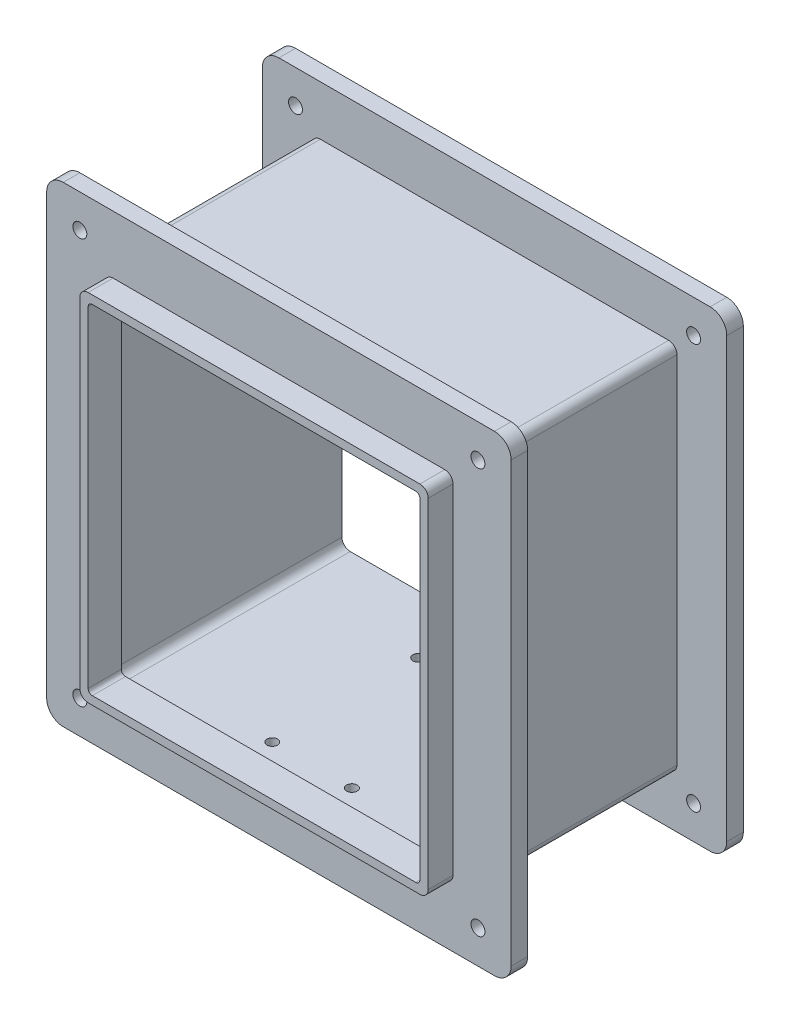
SolidWorks part; units mm, degrees
ref_plane "前视基准面" through (0, 0, 0) normal (0, 0, 1) x (1, 0, 0)
ref_plane "上视基准面" through (0, 0, 0) normal (0, 1, 0) x (1, 0, 0)
ref_plane "右视基准面" through (0, 0, 0) normal (1, 0, 0) x (0, 0, -1)
sketch "草图4" plane through (0, 0, 0) normal (0, 0, 1) x (1, 0, 0)
  line L1 (-105, -107.125) -> (105, -107.125)
  line L2 (-105, -107.125) -> (-105, 107.125)
  line L3 (-105, 107.125) -> (105, 107.125)
  line L4 (105, -107.125) -> (105, 107.125)
  line L5 (-105, -107.125) -> (105, 107.125) construction
  line L6 (-105, 107.125) -> (105, -107.125) construction
  line L7 (-110, -112.125) -> (110, -112.125)
  line L8 (-110, -112.125) -> (-110, 112.125)
  line L9 (-110, 112.125) -> (110, 112.125)
  line L10 (110, -112.125) -> (110, 112.125)
  line L11 (-110, -112.125) -> (110, 112.125) construction
  line L12 (-110, 112.125) -> (110, -112.125) construction
  point P0 (0, 0)
  point P6 (0, 0)
  dimension "D1" = 210
  dimension "D2" = 214.25
  dimension "D3" = 5
  dimension "D4" = 5
extrude "凸台-拉伸7" add sketch "草图4" along normal blind 120
sketch "草图7" plane through (0, 0, 0) normal (0, 0, -1) x (-1, 0, 0)
  line L0 (-110, 112.125) -> (110, 112.125) construction
  line L1 (140, 142.125) -> (-140, 142.125)
  line L2 (140, 142.125) -> (140, -142.125)
  line L3 (140, -142.125) -> (-140, -142.125)
  line L4 (-140, 142.125) -> (-140, -142.125)
  line L5 (140, 142.125) -> (-140, -142.125) construction
  line L6 (140, -142.125) -> (-140, 142.125) construction
  line L7 (-110, -112.125) -> (-110, 112.125) construction
  line L8 (105, -107.125) -> (-105, -107.125) construction
  line L9 (105, 107.125) -> (105, -107.125) construction
  line L10 (-105, 107.125) -> (105, 107.125) construction
  line L11 (-105, -107.125) -> (-105, 107.125) construction
  line L12 (105, -107.125) -> (-105, -107.125)
  line L13 (105, 107.125) -> (105, -107.125)
  line L14 (-105, 107.125) -> (105, 107.125)
  line L15 (-105, -107.125) -> (-105, 107.125)
  point P0 (0, 0)
  dimension "D1" = 30
  dimension "D2" = 30
extrude "凸台-拉伸8" add sketch "草图7" along normal blind 10
sketch "草图8" plane through (0, 0, 120) normal (0, 0, 1) x (1, 0, 0)
  line L1 (140, -142.125) -> (-140, -142.125)
  line L2 (140, -142.125) -> (140, 142.125)
  line L3 (140, 142.125) -> (-140, 142.125)
  line L4 (-140, -142.125) -> (-140, 142.125)
  line L5 (140, -142.125) -> (-140, 142.125) construction
  line L6 (140, 142.125) -> (-140, -142.125) construction
  line L7 (105, -107.125) -> (105, 107.125) construction
  line L8 (-105, -107.125) -> (105, -107.125) construction
  line L9 (-105, 107.125) -> (-105, -107.125) construction
  line L10 (105, 107.125) -> (-105, 107.125) construction
  line L11 (105, -107.125) -> (105, 107.125)
  line L12 (-105, -107.125) -> (105, -107.125)
  line L13 (-105, 107.125) -> (-105, -107.125)
  line L14 (105, 107.125) -> (-105, 107.125)
  point P0 (0, 0)
  point P11 (-117.2762, 126.0676)
extrude "凸台-拉伸9" add sketch "草图8" along normal blind 10
fillet "圆角5" radius 5 8 edges at (-105, 107.125, 60) (-110, 112.125, 60) (105, -107.125, 60) (110, -112.125, 60) (-105, -107.125, 60) (-110, -112.125, 60) (110, 112.125, 60) (105, 107.125, 60)
fillet "圆角6" radius 10 8 edges at (140, 142.125, 125) (140, -142.125, 125) (-140, -142.125, 125) (-140, 142.125, 125) (-140, 142.125, -5) (-140, -142.125, -5) (140, -142.125, -5) (140, 142.125, -5)
hole_wizard "Ø8.4 (8.4) 直径孔1" positions "草图16" profile "草图17" hole size "Ø8.4" standard "GB" end condition through all
sketch "草图16" plane through (0, 0, -10) normal (0, 0, -1) x (-1, 0, 0)
  line L0 (130, 142.125) -> (-130, 142.125) construction
  line L1 (-140, 132.125) -> (-140, -132.125) construction
  line L2 (140, -132.125) -> (140, 132.125) construction
  line L3 (-130, -142.125) -> (130, -142.125) construction
  point P0 (120, -122.125)
  point P3 (120, 122.125)
  point P6 (-120, 122.125)
  point P9 (-120, -122.125)
  dimension "D1" = 20
  dimension "D2" = 20
  dimension "D3" = 20
  dimension "D4" = 20
  dimension "D5" = 20
  dimension "D6" = 20
  dimension "D7" = 20
  dimension "D8" = 20
sketch "草图17" plane through (-120, -122.125, -10) normal (1, 0, 0) x (0, 1, 0)
  line L0 (0, 0) -> (0, 140)
  line L1 (0, 140) -> (4.2, 140)
  line L2 (4.2, 140) -> (4.2, 0)
  line L5 (4.2, 0) -> (0, 0)
  line L11 (0, -6.35) -> (0, 107.95) construction
  dimension "通孔孔直径" = 8.4
  dimension "通孔孔深度" = 140
sketch "草图18" plane through (0, -112.125, 0) normal (0, -1, 0) x (1, 0, 0)
  line L0 (-130, 130) -> (130, 130) construction
  line L5 (105, 0) -> (105, 120) construction
  point P0 (-24, 110)
  point P1 (-24, 22)
  point P2 (24, 22)
  point P3 (24, 110)
  dimension "D1" = 48
  dimension "D2" = 48
  dimension "D3" = 88
  dimension "D4" = 88
  dimension "D5" = 100.2397
  dimension "D6" = 20
  dimension "D7" = 20
  dimension "D8" = 81
hole_wizard "Ø6.4 (6.4) 直径孔1" positions "草图21" profile "草图22" hole size "Ø6.4" standard "GB" end condition up to next
sketch "草图21" plane through (0, -112.125, 0) normal (0, -1, 0) x (-1, 0, 0)
  point P0 (24, -110)
  point P3 (-24, -110)
  point P6 (-24, -22)
  point P9 (24, -22)
sketch "草图22" plane through (-24, -112.125, 110) normal (1, 0, 0) x (0, 0, -1)
  line L0 (0, 0) -> (0, 5)
  line L1 (0, 5) -> (3.2, 5)
  line L2 (3.2, 5) -> (3.2, 0)
  line L5 (3.2, 0) -> (0, 0)
  line L11 (0, -6.35) -> (0, 107.95) construction
  dimension "通孔孔直径" = 6.4
  dimension "通孔孔深度" = 5
sketch "草图24" plane through (0, 0, 130) normal (0, 0, 1) x (1, 0, 0)
  line L0 (105, -102.125) -> (105, 102.125) construction
  line L1 (-100, -107.125) -> (100, -107.125) construction
  line L2 (-105, 102.125) -> (-105, -102.125) construction
  line L3 (100, 107.125) -> (-100, 107.125) construction
  line L4 (105, -102.125) -> (105, 102.125)
  line L5 (-100, -107.125) -> (100, -107.125)
  line L6 (-105, 102.125) -> (-105, -102.125)
  line L7 (100, 107.125) -> (-100, 107.125)
  line L9 (100, -102.125) -> (-100, -102.125)
  line L10 (100, -102.125) -> (100, 102.125)
  line L11 (100, 102.125) -> (-100, 102.125)
  line L12 (-100, -102.125) -> (-100, 102.125)
  line L13 (100, -102.125) -> (-100, 102.125) construction
  line L14 (100, 102.125) -> (-100, -102.125) construction
  arc A0 (105, 102.125) -> (100, 107.125) centre (100, 102.125) ccw construction
  arc A1 (100, -107.125) -> (105, -102.125) centre (100, -102.125) ccw construction
  arc A2 (-105, -102.125) -> (-100, -107.125) centre (-100, -102.125) ccw construction
  arc A3 (-100, 107.125) -> (-105, 102.125) centre (-100, 102.125) ccw construction
  arc A4 (105, 102.125) -> (100, 107.125) centre (100, 102.125) ccw
  arc A5 (100, -107.125) -> (105, -102.125) centre (100, -102.125) ccw
  arc A6 (-105, -102.125) -> (-100, -107.125) centre (-100, -102.125) ccw
  arc A7 (-100, 107.125) -> (-105, 102.125) centre (-100, 102.125) ccw
  point P12 (0, 0)
  dimension "D1" = 5
  dimension "D2" = 5
extrude "凸台-拉伸10" add sketch "草图24" along normal blind 15 separate body
sketch "草图25" plane through (0, 0, 130) normal (0, 0, -1) x (-1, 0, 0)
  line L0 (100, -102.125) -> (-100, -102.125) construction
  line L1 (-100, -102.125) -> (-100, 102.125) construction
  line L2 (100, 102.125) -> (100, -102.125) construction
  line L3 (-100, 102.125) -> (100, 102.125) construction
  line L4 (105, -102.125) -> (105, 102.125) construction
  line L5 (-100, -107.125) -> (100, -107.125) construction
  line L6 (-105, 102.125) -> (-105, -102.125) construction
  line L7 (100, 107.125) -> (-100, 107.125) construction
  line L8 (100, -102.125) -> (-100, -102.125)
  line L9 (-100, -102.125) -> (-100, 102.125)
  line L10 (100, 102.125) -> (100, -102.125)
  line L11 (-100, 102.125) -> (100, 102.125)
  line L12 (105, -102.125) -> (105, 102.125)
  line L13 (-100, -107.125) -> (100, -107.125)
  line L14 (-105, 102.125) -> (-105, -102.125)
  line L15 (100, 107.125) -> (-100, 107.125)
  arc A0 (105, 102.125) -> (100, 107.125) centre (100, 102.125) ccw construction
  arc A1 (100, -107.125) -> (105, -102.125) centre (100, -102.125) ccw construction
  arc A2 (-105, -102.125) -> (-100, -107.125) centre (-100, -102.125) ccw construction
  arc A3 (-100, 107.125) -> (-105, 102.125) centre (-100, 102.125) ccw construction
  arc A4 (105, 102.125) -> (100, 107.125) centre (100, 102.125) ccw
  arc A5 (100, -107.125) -> (105, -102.125) centre (100, -102.125) ccw
  arc A6 (-105, -102.125) -> (-100, -107.125) centre (-100, -102.125) ccw
  arc A7 (-100, 107.125) -> (-105, 102.125) centre (-100, 102.125) ccw
extrude "凸台-拉伸11" add sketch "草图25" along normal blind 5
fillet "圆角7" radius 2.5 12 edges at (103.5355, -105.6605, 125) (105, 0, 125) (103.5355, 105.6605, 125) (0, 107.125, 125) (-103.5355, 105.6605, 125) (-105, 0, 125) (-103.5355, -105.6605, 125) (0, -107.125, 125) (-100, -102.125, 135) (-100, 102.125, 135) (100, 102.125, 135) (100, -102.125, 135)
sketch "草图26" plane through (0, 0, -10) normal (0, 0, -1) x (-1, 0, 0)
  line L0 (-100, 107.125) -> (100, 107.125) construction
  line L1 (108, -110.125) -> (-108, -110.125)
  line L2 (108, -110.125) -> (108, 110.125)
  line L3 (108, 110.125) -> (-108, 110.125)
  line L4 (-108, -110.125) -> (-108, 110.125)
  line L5 (108, -110.125) -> (-108, 110.125) construction
  line L6 (108, 110.125) -> (-108, -110.125) construction
  line L7 (-105, 102.125) -> (-105, -102.125) construction
  line L8 (-100, -107.125) -> (100, -107.125) construction
  line L9 (105, -102.125) -> (105, 102.125) construction
  line L10 (100, -107.125) -> (-100, -107.125) construction
  line L11 (-105, -102.125) -> (-105, 102.125) construction
  line L12 (-100, -107.125) -> (100, -107.125)
  line L13 (105, -102.125) -> (105, 102.125)
  line L14 (100, -107.125) -> (-100, -107.125)
  line L15 (-105, -102.125) -> (-105, 102.125)
  line L16 (-100, 107.125) -> (100, 107.125)
  arc A0 (105, 102.125) -> (100, 107.125) centre (100, 102.125) ccw construction
  arc A1 (100, -107.125) -> (105, -102.125) centre (100, -102.125) ccw construction
  arc A2 (-105, -102.125) -> (-100, -107.125) centre (-100, -102.125) ccw construction
  arc A3 (-100, 107.125) -> (-105, 102.125) centre (-100, 102.125) ccw construction
  arc A4 (105, 102.125) -> (100, 107.125) centre (100, 102.125) ccw
  arc A5 (100, -107.125) -> (105, -102.125) centre (100, -102.125) ccw
  arc A6 (-105, -102.125) -> (-100, -107.125) centre (-100, -102.125) ccw
  arc A7 (-100, 107.125) -> (-105, 102.125) centre (-100, 102.125) ccw
  point P0 (0, 0)
  line M14 (105, 102.125) -> (105, -102.125)
  arc M15 (105, -102.125) -> (100, -107.125) centre (100, -102.125) cw
  line M16 (100, -107.125) -> (-100, -107.125)
  arc M17 (-100, -107.125) -> (-105, -102.125) centre (-100, -102.125) cw
  line M18 (-105, -102.125) -> (-105, 102.125)
  arc M19 (-105, 102.125) -> (-100, 107.125) centre (-100, 102.125) cw
  line M20 (-100, 107.125) -> (100, 107.125)
  arc M21 (100, 107.125) -> (105, 102.125) centre (100, 102.125) cw
  dimension "D1" = 3
  dimension "D2" = 3
extrude "凸台-拉伸12" add sketch "草图26" along normal blind 3 contours L4 L1 L2 L3 M21 M14 M15 M16 M17 M18 M19 M20 region at (0, -109.8165, -10)
fillet "圆角8" radius 5 4 edges at (-108, -110.125, -11.5) (108, -110.125, -11.5) (108, 110.125, -11.5) (-108, 110.125, -11.5)
